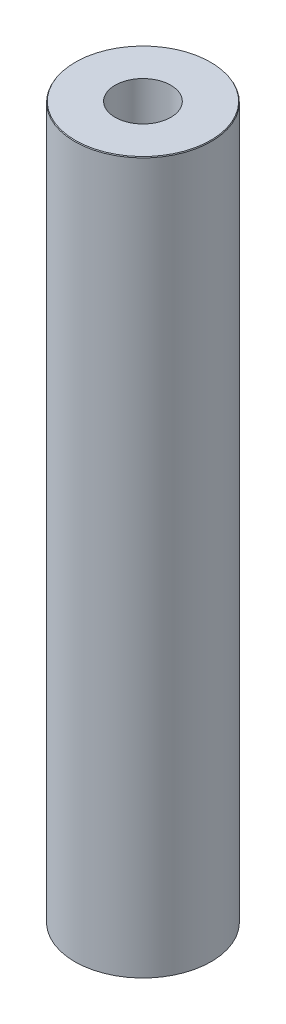
SolidWorks part; units mm, degrees
ref_plane "Front Plane" through (0, 0, 0) normal (0, 0, 1) x (1, 0, 0)
ref_plane "Top Plane" through (0, 0, 0) normal (0, 1, 0) x (1, 0, 0)
ref_plane "Right Plane" through (0, 0, 0) normal (1, 0, 0) x (0, 0, -1)
sketch "Sketch1" plane through (0, 0, 0) normal (0, 1, 0) x (1, 0, 0)
  circle A0 centre (0, 0) radius 57.5
  dimension "SHAFT_OD" = 115
extrude "Boss-Extrude1" add sketch "Sketch1" along normal blind 600
sketch "Sketch2" plane through (0, 0, 0) normal (0, 1, 0) x (1, 0, 0)
  circle A0 centre (0, 0) radius 23.4899
  dimension "BORE_D" = 46.9797
extrude "Cut-Extrude1" cut sketch "Sketch2" along normal through all
chamfer "Chamfer1" distance 0.7275 angle 30 2 edges at (0, 600, 57.5) (0, 0, 57.5) first distance on face at (0, 600, 57.5) first distance on face at (0, 0, 23.4899)
